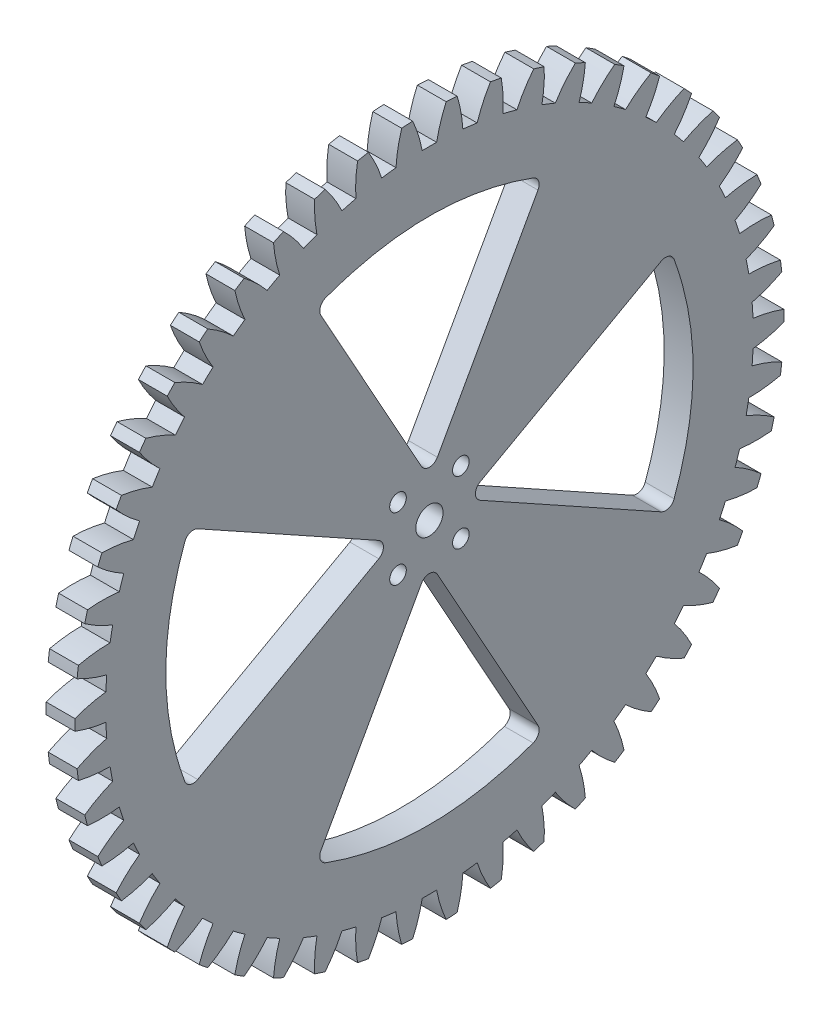
SolidWorks part; units mm, degrees
ref_plane "Plane1" through (0, 0, 0) normal (0, 0, 1) x (1, 0, 0)
ref_plane "Plane2" through (0, 0, 0) normal (0, 1, 0) x (1, 0, 0)
ref_plane "Plane3" through (0, 0, 0) normal (1, 0, 0) x (0, 0, -1)
sketch "HoldingSke" plane through (0, 0, 0) normal (0, 1, 0) x (1, 0, 0)
  line L0 (0, 0) -> (0.2143, -0.2553)
  line L1 (-15, 0) -> (100, 0) construction
  line L2 (0, 0) -> (-2.1039, 2.3779)
  line L3 (0, 0) -> (-11.863, 4.5341)
  line L4 (0, 0) -> (5.5511, 6.6156)
  line L5 (0, 0) -> (-46.8476, -17.4728)
  line L6 (0, 0) -> (-5.2639, -3.5516)
  line L7 (-2.1039, 2.3779) -> (8.6586, 51.2059)
  line L8 (-76.2, 54.61) -> (-75.2, 54.61)
  line L9 (-67.7845, 28.3722) -> (-49.3413, 33.142)
  line L10 (-76.2, 71.12) -> (104.1128, 71.12)
  line L11 (0, 0) -> (-6.35, 0)
  line L12 (-76.2, 101.6) -> (-76.093, 101.6)
  line L13 (24.9733, 27.94) -> (52.9518, 28.4284)
  line L14 (24.9733, 27.94) -> (24.9743, 27.94)
  line L15 (24.9733, 27.94) -> (100.4006, 29.5858)
  line L16 (-63.627, -3) -> (-12.827, -3)
  circle A0 centre (0, 0) radius 3
  circle A1 centre (0, 0) radius 37.5
  circle A2 centre (0, 0) radius 37.5
  circle A3 centre (0, 0) radius 3
  dimension "Num_teeth" = 50
  dimension "Pitch_radius" = 180.3128
  dimension "Width" = 6.35
  dimension "Thickness" = 6.35
sketch "BasProSke" plane through (0, 0, 0) normal (0, 1, 0) x (1, 0, 0)
  line L0 (-10, 0) -> (60, 0) construction
  line L1 (0, 0) -> (0, 78)
  line L2 (0, 0) -> (6.35, 0)
  line L3 (6.35, 0) -> (6.35, 78)
  line L4 (6.35, 78) -> (0, 78)
  dimension "Thickness" = 6.35
  dimension "Diameter" = 156
revolve "Base-Revolve" add sketch "BasProSke" angle 360 about L0
sketch "TooCutSke" plane through (0, 0, 0) normal (1, 0, 0) x (0, 0, -1)
  line L1 (0, 0) -> (0, 107) construction
  line L2 (0, 0) -> (-2.543, 74.9569) construction
  line L3 (0, 0) -> (-9.4146, 149.6414) construction
  line L4 (-2.543, 74.9569) -> (-4.7073, 74.8207) construction
  arc A0 (1.5844, 71.2314) -> (-1.5844, 71.2314) centre (0, 0) ccw
  arc A1 (3.6968, 77.9378) -> (-3.6968, 77.9378) centre (0, 0) ccw
  circle A2 centre (0, 0) radius 75 construction
  circle A3 centre (0, 0) radius 72.6111 construction
  arc A4 (-1.5844, 71.2314) -> (-3.6968, 77.9378) centre (-31.0576, 65.6338) ccw
  arc A5 (3.6968, 77.9378) -> (1.5844, 71.2314) centre (31.0576, 65.6338) ccw
extrude "ToothCut" cut sketch "TooCutSke" along normal through all
fillet "Breaks" [suppressed] radius 0.06 tangent propagation no
fillet "RootFillets" [suppressed] radius 0.751
pattern_circular "TeethCuts" count 50 every 7.2 about axis through (-10, 0, 0) along (1, 0, 0) of "ToothCut", "RootFillets", "Breaks"
sketch "HubNeaOneSke" plane through (0, 0, 0) normal (-1, 0, 0) x (0, 0, 1)
  circle A0 centre (0, 0) radius 37.5
  dimension "Diameter" = 75
extrude "HubNearOne" [suppressed] add sketch "HubNeaOneSke" along normal blind 43.6501
sketch "HubNeaBotSke" plane through (0, 0, 0) normal (-1, 0, 0) x (0, 0, 1)
  circle A0 centre (0, 0) radius 37.5
  dimension "Diameter" = 75
extrude "HubNearBoth" [suppressed] add sketch "HubNeaBotSke" along normal blind 21.825
ref_plane "FarPln" through (6.35, 0, 0) normal (1, 0, 0) x (0, 0, -1)
sketch "HubFarSke" plane through (6.35, 0, 0) normal (1, 0, 0) x (0, 0, -1)
  circle A0 centre (0, 0) radius 37.5
  dimension "Diameter" = 75
extrude "HubFar" [suppressed] add sketch "HubFarSke" along normal blind 21.825
sketch "BorSke" plane through (0, 0, 0) normal (1, 0, 0) x (0, 0, -1)
  circle A0 centre (0, 0) radius 3
  dimension "Diameter" = 6
extrude "Bore" cut sketch "BorSke" along normal mid plane 100.0001
sketch "KeySke" plane through (0, 0, 0) normal (1, 0, 0) x (0, 0, -1)
  line L0 (-1, 0) -> (-1, 4)
  line L1 (-1, 4) -> (1, 4)
  line L2 (1, 4) -> (1, 0)
  line L3 (0, 0) -> (0, 34) construction
  line L4 (-1, 0) -> (1, 0)
  dimension "Width" = 2
extrude "Keyway" [suppressed] cut sketch "KeySke" along normal mid plane 100.0001
pattern_circular "Keyway2" [suppressed] count 2 every 90 about axis through (-10, 0, 0) along (1, 0, 0) reverse direction yes
sketch "Esquisse1" plane through (0, 0, 0) normal (-1, 0, 0) x (0, 0, 1)
  circle A0 centre (6.9148, 6.9148) radius 1.83
  dimension "D1" = 3.66
extrude "Enlèv. mat.-Extru.1" cut sketch "Esquisse1" against normal up to next
pattern_circular "Répétition circulaire1" count 4 every 90 about axis through (0, 0, 0) along (-1, 0, 0) of "Enlèv. mat.-Extru.1"
sketch "Esquisse2" plane through (6.35, 0, 0) normal (1, 0, 0) x (0, 0, -1)
  line L0 (-53, 25) -> (-8, 0)
  line L1 (-8, 0) -> (-53, -25)
  line L2 (-53, -25) -> (-53, 25) construction
  line L3 (-53, 0) -> (-8, 0) construction
  line L4 (50, 0) -> (-50, 0) construction
  circle A0 centre (0, 0) radius 3 construction
  spline S0 degree 2 poles (-53, 25) (-63, 0) (-53, -25) knots 0 0 0 1 1 1
  dimension "D4" = 8
  dimension "D1" = 45
  dimension "D2" = 50
  dimension "D3" = 5
extrude "Enlèv. mat.-Extru.2" cut sketch "Esquisse2" against normal up to next
fillet "Congé1" radius 2 3 edges at (3.175, -25, 53) (3.175, 25, 53) (3.175, 0, 8)
pattern_circular "Répétition circulaire2" count 4 every 90 about axis through (6.35, 0, 0) along (1, 0, 0) of "Congé1", "Enlèv. mat.-Extru.2"
equation "' \"Module@HoldingSke\" = 6.35"
equation "' \"Num_teeth@HoldingSke\" = 12"
equation "' \"Ap@HoldingSke\" =  20"
equation "' \"Ap@HoldingSke\" = 20"
equation "' \"Width@HoldingSke\" = 0.5 * 25.4"
equation "' \"Hub_dia@HoldingSke\"= 1 * 25.4"
equation "' \"Hub_dia@HoldingSke\" = 1 * 25.4"
equation "' \"Overall_len@HoldingSke\" = 1.0 * 25.4"
equation "' \"Bore@HoldingSke\" = 0.75 * 25.4"
equation "' \"T_dim@HoldingSke\" = 0.1 * 25.4"
equation "' \"Width@KeySke\" = 0.25 * 25.4"
equation "' \"Show_teeth@HoldingSke\" = 13"
equation "' \"Backlash@HoldingSke\" = 0.009 * 25.4"
equation "' \"Addendum_fac@HoldingSke\" = 1.0"
equation "' \"Dedendum_fac@HoldingSke\" = 1.25"
equation "' \"Dedendum_add@HoldingSke\" = 0.00005 * 25.4"
equation "' \"Clearance_fac@HoldingSke\" = 0.25"
equation "\"Pitch@HoldingSke\" = 1 / \"Module@HoldingSke\""
equation "\"Overcut_dia@TooCutSke\" = (\"Num_teeth@HoldingSke\" + 2 * \"Addendum_fac@HoldingSke\") / \"Pitch@HoldingSke\" + 0.002 * 25.4"
equation "\"Pitch_dia@TooCutSke\" = \"Num_teeth@HoldingSke\" / \"Pitch@HoldingSke\""
equation "\"Base_dia@TooCutSke\" = \"Num_teeth@HoldingSke\" / \"Pitch@HoldingSke\" * cos((\"Ap@HoldingSke\"  * 3.14159265 / 180))"
equation "\"Root_dia@TooCutSke\" = (\"Num_teeth@HoldingSke\" + 2) / \"Pitch@HoldingSke\" - 2 * (\"Addendum_fac@HoldingSke\" + \"Dedendum_fac@HoldingSke\") / \"Pitch@HoldingSke\" - \"Dedendum_add@HoldingSke\" * 2"
equation "\"Half_ang@TooCutSke\" = 180 / \"Num_teeth@HoldingSke\""
equation "\"Half_CT@TooCutSke\" = \"Num_teeth@HoldingSke\" / \"Pitch@HoldingSke\" * sin((3.14159265 / 2 / \"Num_teeth@HoldingSke\")) / 2 - 7 * \"Backlash@HoldingSke\" / 4"
equation "\"Flank_rad@TooCutSke\" = \"Num_teeth@HoldingSke\" / \"Pitch@HoldingSke\" / 5"
equation "\"Radius@RootFillets\" = \"Clearance_fac@HoldingSke\" / \"Pitch@HoldingSke\" + \"Dedendum_add@HoldingSke\""
equation "\"Break_rad@Breaks\" = 0.02 / \"Pitch@HoldingSke\""
equation "\"Thickness@HoldingSke\" = \"Width@HoldingSke\""
equation "\"OAL@HoldingSke\" = \"Thickness@HoldingSke\""
equation "\"MHD@HoldingSke\" = (\"Num_teeth@HoldingSke\" + 2) / \"Pitch@HoldingSke\" - 2 * (\"Addendum_fac@HoldingSke\" + \"Dedendum_fac@HoldingSke\")  / \"Pitch@HoldingSke\" - \"Dedendum_add@HoldingSke\" * 2"
equation "\"MBD@HoldingSke\" = (\"Num_teeth@HoldingSke\" + 2) / \"Pitch@HoldingSke\" - 2 * (\"Addendum_fac@HoldingSke\" + \"Dedendum_fac@HoldingSke\")  / \"Pitch@HoldingSke\" - \"Dedendum_add@HoldingSke\" * 2 - 0.002 * 25.4"
equation "\"MHD@HoldingSke\" = ((sgn( \"MHD@HoldingSke\" - \"Hub_dia@HoldingSke\" )-1)*( \"MHD@HoldingSke\" - \"Hub_dia@HoldingSke\" ))/-2+ \"Hub_dia@HoldingSke\""
equation "\"MBD@HoldingSke\" = ((sgn( \"MBD@HoldingSke\" - \"Bore@HoldingSke\" )-1)*( \"MBD@HoldingSke\" - \"Bore@HoldingSke\" ))/-2+ \"Bore@HoldingSke\""
equation "\"OAL@HoldingSke\" = ((sgn( \"OAL@HoldingSke\" - \"Overall_len@HoldingSke\" )+1)*( \"OAL@HoldingSke\" - \"Overall_len@HoldingSke\" ))/2 + \"Overall_len@HoldingSke\" + 0.000002 * 25.4"
equation "\"Num_teeth@TeethCuts\" = int( \"Show_teeth@HoldingSke\" ) + 1"
equation "\"Num_teeth@TeethCuts\" = ((sgn( \"Num_teeth@TeethCuts\" - \"Num_teeth@HoldingSke\" )-1)*( \"Num_teeth@TeethCuts\" - \"Num_teeth@HoldingSke\" ))/-2+ \"Num_teeth@HoldingSke\""
equation "\"Num_teeth@TeethCuts\" = ((sgn( \"Num_teeth@TeethCuts\" - 2.0)+1)*( \"Num_teeth@TeethCuts\" - 2.0))/2 +2.0"
equation "\"Angle@TeethCuts\" = 360.0 / \"Num_teeth@HoldingSke\""
equation "\"Diameter@BasProSke\" = (\"Num_teeth@HoldingSke\" + 2 * \"Addendum_fac@HoldingSke\") / \"Pitch@HoldingSke\""
equation "\"Thickness@BasProSke\"  = \"Thickness@HoldingSke\""
equation "' \"Fillet_rad@BasProSke\" =  \"Thickness@HoldingSke\" * 0.05"
equation "' \"Fillet_rad@BasProSke\" = \"Thickness@HoldingSke\" * 0.05"
equation "\"MHD@HoldingSke\" = ((sgn( \"MHD@HoldingSke\" - \"Root_dia@TooCutSke\" )-1)*( \"MHD@HoldingSke\" - \"Root_dia@TooCutSke\" ))/-2+ \"Root_dia@TooCutSke\""
equation "\"Diameter@HubNeaOneSke\" = \"MHD@HoldingSke\""
equation "\"Length@HubNearOne\" = \"OAL@HoldingSke\" - \"Thickness@BasProSke\""
equation "\"Diameter@HubNeaBotSke\" = \"MHD@HoldingSke\""
equation "\"Length@HubNearBoth\" = ( \"OAL@HoldingSke\" - \"Thickness@BasProSke\" ) / 2.0"
equation "\"Thickness@FarPln\" = \"Thickness@BasProSke\""
equation "\"Diameter@HubFarSke\" = \"MHD@HoldingSke\""
equation "\"Length@HubFar\" = ( \"OAL@HoldingSke\" - \"Thickness@BasProSke\" ) / 2.0"
equation "\"Diameter@BorSke\" = \"MBD@HoldingSke\""
equation "\"D1@Bore\" = \"OAL@HoldingSke\" * 2.0"
equation "\"D1@Keyway\" = \"OAL@HoldingSke\" * 2.0"
equation "\"Offset@KeySke\" = \"T_dim@HoldingSke\" + \"MBD@HoldingSke\" / 2.0"
